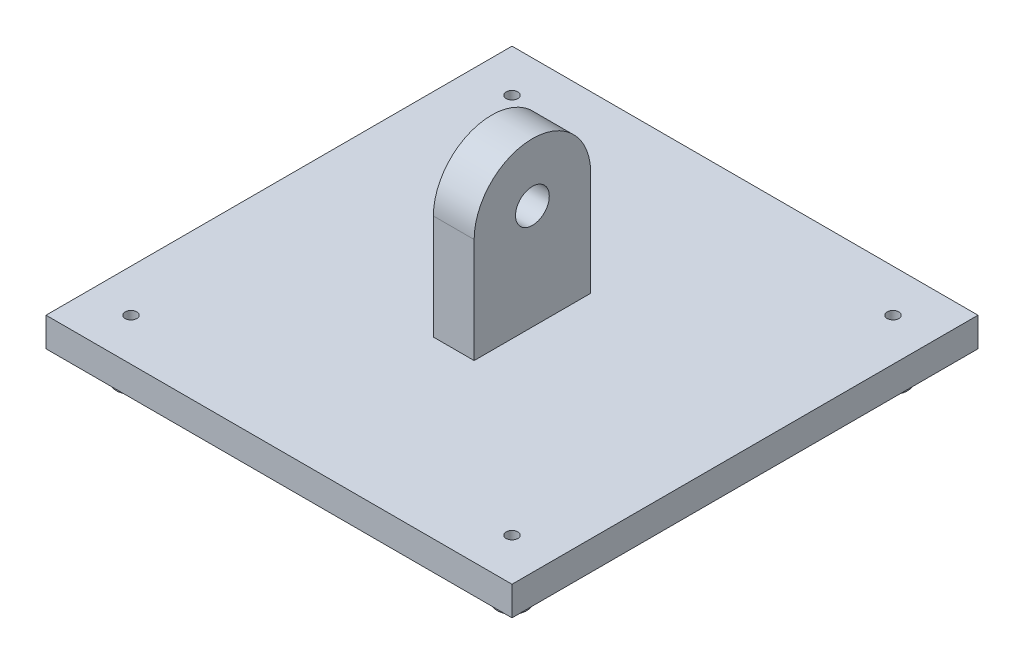
SolidWorks part; units mm, degrees
ref_plane "Front Plane" through (0, 0, 0) normal (0, 0, 1) x (1, 0, 0)
ref_plane "Top Plane" through (0, 0, 0) normal (0, 1, 0) x (1, 0, 0)
ref_plane "Right Plane" through (0, 0, 0) normal (1, 0, 0) x (0, 0, -1)
sketch "Sketch2" plane through (0, 0, 0) normal (0, 1, 0) x (1, 0, 0)
  line L1 (-40, -40) -> (40, -40)
  line L2 (-40, -40) -> (-40, 40)
  line L3 (-40, 40) -> (40, 40)
  line L4 (40, -40) -> (40, 40)
  line L5 (-40, -40) -> (40, 40) construction
  line L6 (-40, 40) -> (40, -40) construction
  point P0 (0, 0)
  dimension "D1" = 80
  dimension "D2" = 80
extrude "Boss-Extrude1" add sketch "Sketch2" along normal blind 5
sketch "Sketch9" plane through (0, 0, 0) normal (0, -1, 0) x (1, 0, 0)
  line L0 (0, 0) -> (0, -40)
  line L1 (40, -40) -> (-40, -40) construction
  circle A0 centre (-32.705, 32.705) radius 2.5
  circle A1 centre (32.705, 32.705) radius 2.5
  circle A2 centre (-32.705, -32.705) radius 2.5
  circle A3 centre (32.705, -32.705) radius 2.5
  dimension "D2" = 32.705
  dimension "D3" = 5
  dimension "D5" = 32.705
  dimension "D1" = 32.705
  dimension "D4" = 32.705
extrude "Boss-Extrude3" add sketch "Sketch9" along normal blind 5 contours A0 | A1 | A3 | A2
sketch "Sketch10" plane through (0, -5, 0) normal (0, -1, 0) x (1, 0, 0)
  circle A0 centre (-32.705, -32.705) radius 1
  circle A1 centre (-32.705, 32.705) radius 1
  circle A2 centre (32.705, 32.705) radius 1
  circle A3 centre (32.705, -32.705) radius 1
  dimension "D1" = 2
extrude "Cut-Extrude6" cut sketch "Sketch10" against normal through all
sketch "Sketch11" plane through (40, 0, 0) normal (1, 0, 0) x (0, 0, -1)
  line L0 (-10, 5) -> (-10, 23)
  line L1 (-40, 5) -> (40, 5) construction
  line L2 (-10, 5) -> (10, 5)
  line L3 (10, 5) -> (10, 23)
  arc A0 (10, 23) -> (-10, 23) centre (0, 23) ccw
  circle A1 centre (0, 23) radius 2.9
  point P8 (0, 5)
  dimension "D2" = 18
  dimension "D3" = 5.8
  dimension "D1" = 20
extrude "Boss-Extrude4" add sketch "Sketch11" against normal up to surface (80 mm away) up to face at (-40, 2.5, 0)
sketch "Sketch12" plane through (0, 5, 0) normal (0, 1, 0) x (1, 0, 0)
  line L0 (-3.5, -10) -> (3.5, -10)
  line L1 (-40, -10) -> (40, -10) construction
  line L2 (3.5, -10) -> (3.5, 10)
  line L3 (-40, 10) -> (40, 10) construction
  line L4 (3.5, 10) -> (-3.5, 10)
  line L5 (-3.5, 10) -> (-3.5, -10)
  line L6 (40, 40) -> (-40, 40)
  line L7 (-40, 40) -> (-40, -40)
  line L8 (-40, -40) -> (40, -40)
  line L9 (40, -40) -> (40, 40)
  point P14 (0, 10)
  dimension "D1" = 7
extrude "Cut-Extrude7" cut sketch "Sketch12" along normal through all
